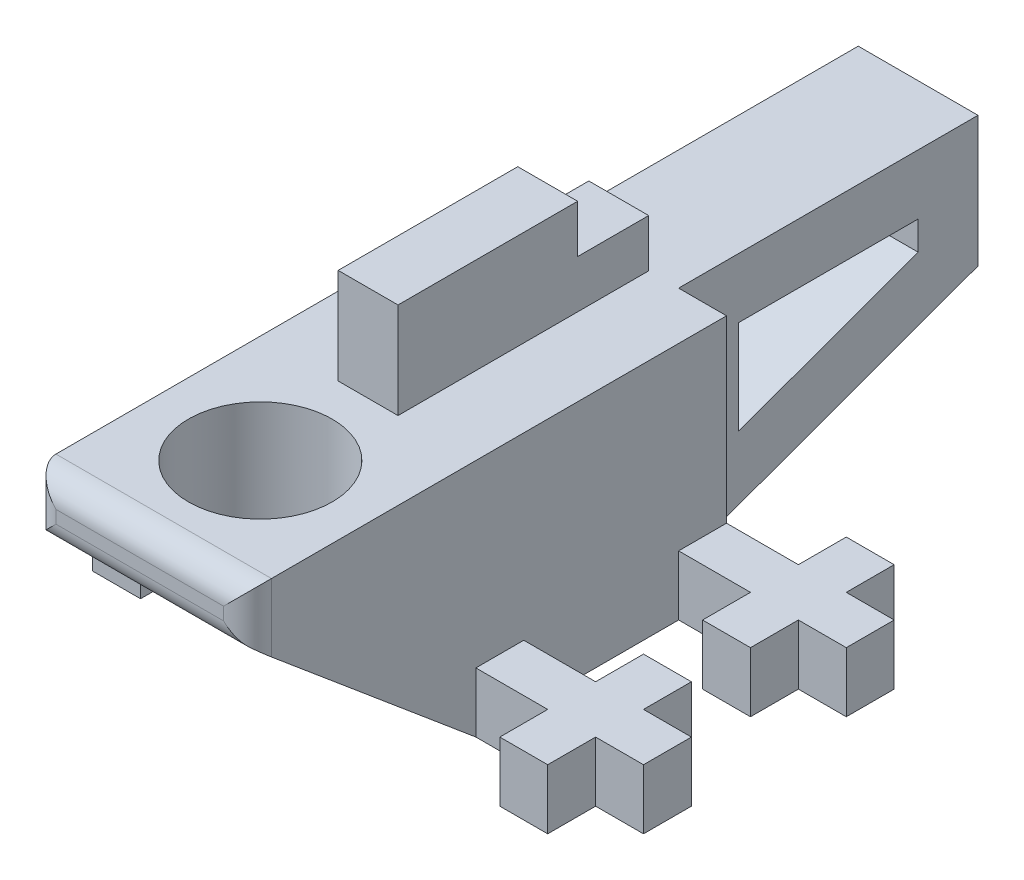
SolidWorks part; units mm, degrees
ref_plane "Спереди" through (0, 0, 0) normal (0, 0, 1) x (1, 0, 0)
ref_plane "Сверху" through (0, 0, 0) normal (0, 1, 0) x (1, 0, 0)
ref_plane "Справа" through (0, 0, 0) normal (1, 0, 0) x (0, 0, -1)
sketch "Эскиз1" plane through (0, 0, 0) normal (1, 0, 0) x (0, 0, -1)
  line L0 (0, 0) -> (-19.0681, 16)
  line L1 (-19.0681, 16) -> (-19.0681, 20)
  line L2 (-19.0681, 20) -> (8.0825, 20)
  line L4 (8.0825, 0) -> (0, 0)
  line L5 (8.0825, 20) -> (30, 20)
  line L6 (20.9319, 0) -> (20.9319, 20)
  line L7 (30, 0) -> (8.0825, 0)
  line L8 (30, 0) -> (20.9319, 0)
  line L9 (20.9319, 0) -> (45.9319, 9.0993)
  line L10 (45.9319, 9.0993) -> (45.9319, 20)
  line L11 (45.9319, 20) -> (30, 20)
  line L18 (25.9319, 7.1407) -> (25.9319, 15)
  line L19 (25.9319, 15) -> (40.9319, 15)
  line L20 (40.9319, 15) -> (40.9319, 12.6003)
  line L21 (40.9319, 12.6003) -> (25.9319, 7.1407)
  dimension "D1" = 20
  dimension "D2" = 140
  dimension "D3" = 40
  dimension "D4" = 4
  dimension "D5" = 160
  dimension "D6" = 15
  dimension "D7" = 5
  dimension "D8" = 5
  dimension "D9" = 25
  dimension "D10" = 5
extrude "Бобышка-Вытянуть1" add sketch "Эскиз1" along normal mid plane 18 contours L7 L6 L5 L2 L1 L0 L4 region at (0, 11.0995, -4.1465)
extrude "Бобышка-Вытянуть2" add sketch "Эскиз1<3>" along normal mid plane 10 contours L10 L11 L5 L6 L9 L20 L21 L18 L19 region at (0, 10, -21.2521)
sketch "Эскиз1<3>" plane through (0, 0, 0) normal (1, 0, 0) x (0, 0, -1) same geometry as "Эскиз1"
sketch "Эскиз3" plane through (0, 20, 0) normal (0, 1, 0) x (1, 0, 0)
  line L0 (-9, -19.0681) -> (-9, 20.9319) construction
  circle A0 centre (0, -9) radius 6
  point P2 (0, 0)
  point P4 (0, 0)
  dimension "D2" = 12
  dimension "D1" = 9
  dimension "D3" = 9
extrude "Вырез-Вытянуть1" cut sketch "Эскиз3" against normal blind 30
fillet "Скругление1" radius 2 4 edges at (0, 20, 19.0681) (9, 18, 19.0681) (0, 16, 19.0681) (-9, 18, 19.0681)
sketch "Эскиз4" plane through (0, 0, 0) normal (0, -1, 0) x (1, 0, 0)
  line L0 (9, 0) -> (15, 0)
  line L1 (15, 0) -> (15, 4)
  line L2 (15, 4) -> (19, 4)
  line L3 (19, 4) -> (19, 0)
  line L4 (19, 0) -> (23, 0)
  line L5 (23, 0) -> (23, -4)
  line L6 (23, -4) -> (19, -4)
  line L7 (19, -4) -> (19, -8)
  line L8 (19, -8) -> (15, -8)
  line L9 (15, -8) -> (15, -4)
  line L10 (15, -4) -> (9, -4)
  line L11 (9, -20.9319) -> (9, 0) construction
  line L12 (9, -4) -> (9, 0)
  line L13 (0, 0) -> (0, -20.9319) construction
  line L14 (5, -20.9319) -> (-5, -20.9319) construction
  line L15 (-23, 0) -> (-23, -4)
  line L16 (-9, -4) -> (-9, 0)
  line L17 (-15, -4) -> (-9, -4)
  line L18 (-15, -8) -> (-15, -4)
  line L19 (-19, -4) -> (-19, -8)
  line L20 (-19, -8) -> (-15, -8)
  line L21 (-23, -4) -> (-19, -4)
  line L22 (-19, 0) -> (-23, 0)
  line L23 (-19, 4) -> (-19, 0)
  line L24 (-15, 4) -> (-19, 4)
  line L25 (-15, 0) -> (-15, 4)
  line L26 (-9, 0) -> (-15, 0)
  line L27 (-9, -10.466) -> (9, -10.466) construction
  line L28 (-9, -20.9319) -> (-9, 0) construction
  line L29 (15, -16.9319) -> (9, -16.9319)
  line L30 (15, -12.9319) -> (15, -16.9319)
  line L31 (19, -12.9319) -> (15, -12.9319)
  line L32 (19, -16.9319) -> (19, -12.9319)
  line L33 (23, -16.9319) -> (19, -16.9319)
  line L34 (23, -20.9319) -> (23, -16.9319)
  line L35 (19, -20.9319) -> (23, -20.9319)
  line L36 (19, -24.9319) -> (19, -20.9319)
  line L37 (15, -24.9319) -> (19, -24.9319)
  line L38 (15, -20.9319) -> (15, -24.9319)
  line L39 (9, -20.9319) -> (15, -20.9319)
  line L40 (9, -16.9319) -> (9, -20.9319)
  line L41 (-19, -20.9319) -> (-23, -20.9319)
  line L42 (-19, -24.9319) -> (-19, -20.9319)
  line L43 (-15, -24.9319) -> (-19, -24.9319)
  line L44 (-15, -20.9319) -> (-15, -24.9319)
  line L45 (-9, -20.9319) -> (-15, -20.9319)
  line L46 (-9, -16.9319) -> (-9, -20.9319)
  line L47 (-15, -16.9319) -> (-9, -16.9319)
  line L48 (-15, -12.9319) -> (-15, -16.9319)
  line L49 (-19, -12.9319) -> (-15, -12.9319)
  line L50 (-19, -16.9319) -> (-19, -12.9319)
  line L51 (-23, -16.9319) -> (-19, -16.9319)
  line L52 (-23, -20.9319) -> (-23, -16.9319)
  dimension "D1" = 6
  dimension "D2" = 4
  dimension "D3" = 4
  dimension "D4" = 4
  dimension "D5" = 6
  dimension "D6" = 4
  dimension "D7" = 4
  dimension "D8" = 4
  dimension "D9" = 4
extrude "Бобышка-Вытянуть3" add sketch "Эскиз4" against normal blind 5
ref_plane "Плоскость4" through (0, 0, 0) normal (1, 0, 0) x (0, 0, -1)
sketch "Эскиз5" plane through (0, 0, 0) normal (1, 0, 0) x (0, 0, -1)
  line L0 (0, 20) -> (0, 28)
  line L1 (-17.0681, 20) -> (20.9319, 20) construction
  line L3 (20.9319, 24) -> (20.9319, 20)
  line L4 (20.9319, 20) -> (0, 20)
  line L5 (0, 28) -> (15, 28)
  line L6 (15, 28) -> (15, 24)
  line L7 (15, 24) -> (20.9319, 24)
  dimension "D1" = 8
  dimension "D2" = 4
  dimension "D3" = 15
extrude "Бобышка-Вытянуть5" add sketch "Эскиз5" along normal mid plane 5
